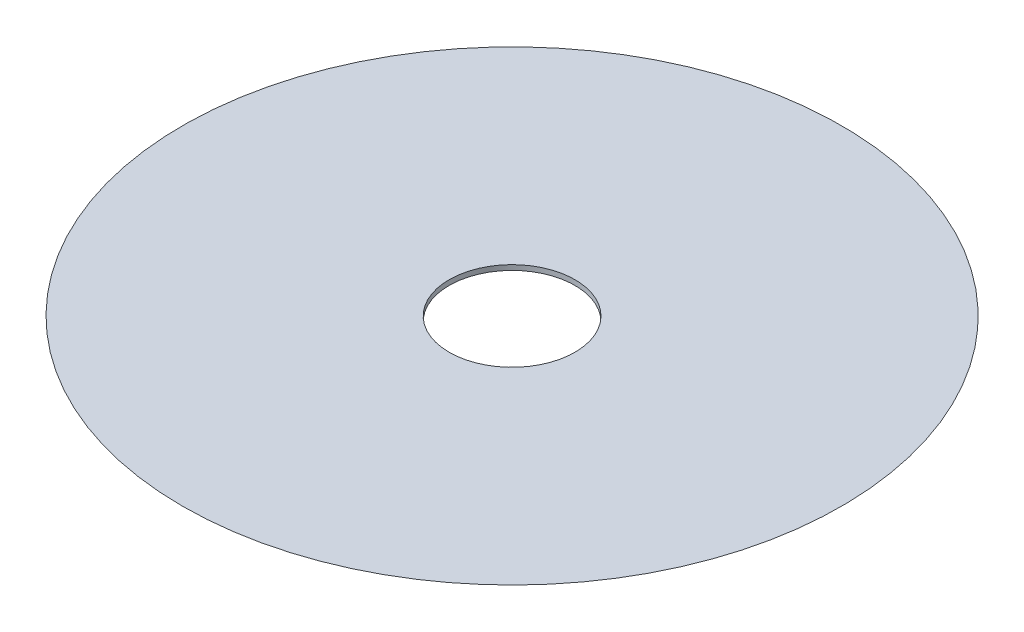
SolidWorks part; units mm, degrees
ref_plane "Front Plane" through (0, 0, 0) normal (0, 0, 1) x (1, 0, 0)
ref_plane "Top Plane" through (0, 0, 0) normal (0, 1, 0) x (1, 0, 0)
ref_plane "Right Plane" through (0, 0, 0) normal (1, 0, 0) x (0, 0, -1)
sketch "Sketch1" plane through (0, 0, 0) normal (0, 1, 0) x (1, 0, 0)
  circle A0 centre (0, 0) radius 65.5
  dimension "D1" = 131
extrude "Boss-Extrude1" add sketch "Sketch1" along normal blind 1
sketch "Sketch2" plane through (0, 1, 0) normal (0, 1, 0) x (1, 0, 0)
  circle A0 centre (0, 0) radius 12.5
  dimension "D1" = 25
extrude "Cut-Extrude1" cut sketch "Sketch2" against normal blind 5
fillet "Fillet1" radius 10 1 edges at (0, 0, 65.5)
